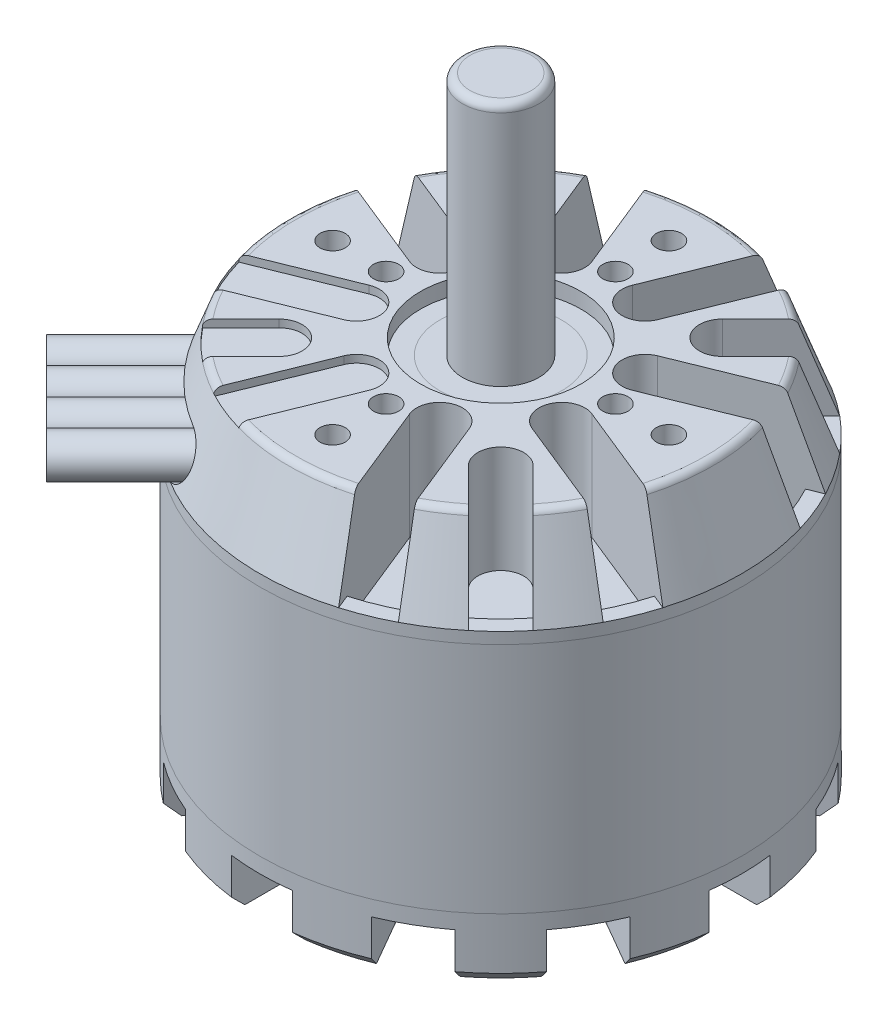
SolidWorks part; units mm, degrees
ref_plane "Front" through (0, 0, 0) normal (0, 0, 1) x (1, 0, 0)
ref_plane "Top" through (0, 0, 0) normal (0, 1, 0) x (1, 0, 0)
ref_plane "Right" through (0, 0, 0) normal (1, 0, 0) x (0, 0, -1)
sketch "Sketch1" plane through (0, 0, 0) normal (0, 1, 0) x (1, 0, 0)
  circle A0 centre (0, 0) radius 31.5
  dimension "D1" = 63
extrude "Boss-Extrude1" add sketch "Sketch1" along normal blind 51.5
sketch "Sketch2" plane through (0, 0, 0) normal (0, -1, 0) x (1, 0, 0)
  circle A0 centre (0, 0) radius 14
  dimension "D1" = 28
extrude "Boss-Extrude2" add sketch "Sketch2" along normal blind 1.5
sketch "Sketch3" plane through (0, -1.5, 0) normal (0, -1, 0) x (1, 0, 0)
  point P0 (0, 11)
  point P5 (11, 0)
  point P6 (0, -11)
  point P7 (-11, 0)
  point P8 (0, 0)
  dimension "D1" = 11
  dimension "D2" = 4
hole_wizard "M4 Tapped Hole1" positions "Sketch5" profile "Sketch4" tap size "M4" standard "ISO"
sketch "Sketch5" plane through (0, -1.5, 0) normal (0, -1, 0) x (-1, 0, 0)
  point P0 (0, -11)
  point P3 (-11, 0)
  point P6 (0, 11)
  point P9 (11, 0)
sketch "Sketch4" plane through (0, -1.5, 11) normal (1, 0, 0) x (0, 0, -1)
  line L0 (0, 0) -> (0, 12.4914)
  line L1 (0, 12.4914) -> (1.65, 11.5)
  line L2 (1.65, 11.5) -> (1.65, 0)
  line L5 (1.65, 0) -> (0, 0)
  line L10 (0, 12.4914) -> (-1.65, 11.5) construction
  line L11 (0, -6.35) -> (0, 107.95) construction
  dimension "Tap Drill Dia." = 3.3
  dimension "Tap Drill Depth" = 11.5
  dimension "Drill Angle" = 118
cosmetic thread "Hole Thread1" parameters "D1"=8, "D2"=4
cosmetic thread "Hole Thread2" parameters "D1"=8, "D2"=4
cosmetic thread "Hole Thread3" parameters "D1"=8, "D2"=4
cosmetic thread "Hole Thread4" parameters "D1"=8, "D2"=4
sketch "Sketch6" plane through (0, 0, 0) normal (0, -1, 0) x (1, 0, 0)
  line L0 (0, 31.5) -> (0, 18) construction
  line L1 (-4, 18) -> (-4, 31.245)
  line L2 (4, 18) -> (4, 31.245)
  line L3 (18, 4) -> (31.245, 4)
  line L4 (18, -4) -> (31.245, -4)
  line L5 (31.5, 0) -> (18, 0) construction
  line L6 (4, -18) -> (4, -31.245)
  line L7 (-4, -18) -> (-4, -31.245)
  line L8 (0, -31.5) -> (0, -18) construction
  line L9 (-18, -4) -> (-31.245, -4)
  line L10 (-18, 4) -> (-31.245, 4)
  line L11 (-31.5, 0) -> (-18, 0) construction
  line L12 (0, 0) -> (-15.75, 27.2798) construction
  line L13 (-19.0866, 25.059) -> (-14.9641, 17.9186)
  line L14 (-12.1584, 29.059) -> (-8.0359, 21.9186)
  line L15 (25.059, 19.0866) -> (17.9186, 14.9641)
  line L16 (29.059, 12.1584) -> (21.9186, 8.0359)
  line L17 (0, 0) -> (27.2798, 15.75) construction
  line L18 (19.0866, -25.059) -> (14.9641, -17.9186)
  line L19 (12.1584, -29.059) -> (8.0359, -21.9186)
  line L20 (0, 0) -> (15.75, -27.2798) construction
  line L21 (-25.059, -19.0866) -> (-17.9186, -14.9641)
  line L22 (-29.059, -12.1584) -> (-21.9186, -8.0359)
  line L23 (0, 0) -> (-27.2798, -15.75) construction
  line L24 (-22.2739, 22.2739) -> (22.2739, -22.2739) construction
  line L25 (-25.059, 19.0866) -> (-17.9186, 14.9641)
  line L26 (-29.059, 12.1584) -> (-21.9186, 8.0359)
  line L27 (19.0866, 25.059) -> (14.9641, 17.9186)
  line L28 (12.1584, 29.059) -> (8.0359, 21.9186)
  line L29 (25.059, -19.0866) -> (17.9186, -14.9641)
  line L30 (29.059, -12.1584) -> (21.9186, -8.0359)
  line L31 (-19.0866, -25.059) -> (-14.9641, -17.9186)
  line L32 (-12.1584, -29.059) -> (-8.0359, -21.9186)
  circle A0 centre (0, 0) radius 31.5 construction
  circle A1 centre (0, 18) radius 4
  circle A2 centre (0, 0) radius 14 construction
  circle A3 centre (0, 0) radius 31.5
  circle A4 centre (18, 0) radius 4
  circle A5 centre (0, -18) radius 4
  circle A6 centre (-18, 0) radius 4
  circle A7 centre (-11.5, 19.9186) radius 4
  circle A8 centre (19.9186, 11.5) radius 4
  circle A9 centre (11.5, -19.9186) radius 4
  circle A10 centre (-19.9186, -11.5) radius 4
  circle A11 centre (-19.9186, 11.5) radius 4
  circle A12 centre (11.5, 19.9186) radius 4
  circle A13 centre (19.9186, -11.5) radius 4
  circle A14 centre (-11.5, -19.9186) radius 4
  point P38 (0, 0)
  point P67 (0, 0)
  point P93 (0, 0)
  circle M11 centre (0, 0) radius 31.5
  dimension "D1" = 8
  dimension "D4" = 8
  dimension "D3" = 30
  dimension "D5" = 8.5
  dimension "D7" = 15
  dimension "D2" = 4
  dimension "D6" = 4
  dimension "D8" = 4
extrude "Cut-Extrude1" cut sketch "Sketch6" against normal blind 10 contours A7 L14 L13 M11 | A7 | A1 L2 L1 M11 | A1 | L28 A12 L27 M11 | A12 | A8 L16 L15 M11 | A8 | A4 L4 L3 M11 | A4 | A13 | L30 A13 L29 M11 | A9 | A9 L19 L18 M11 | A5 | A5 L7 L6 M11 | A14 | L32 A14 L31 M11 | A10 | A10 L22 L21 M11 | A6 | A6 L10 L9 M11 | A11 | L26 A11 L25 M11 region at (0, 0, 26.2399) region at (0, 0, 18) region at (-14.3517, 0, 24.8578) region at (14.3517, 0, 24.8578) region at (-11.5, 0, 19.9186) region at (11.5, 0, 19.9186) region at (-24.8578, 0, 14.3517) region at (24.8578, 0, 14.3517) region at (-19.9186, 0, 11.5) region at (19.9186, 0, 11.5) region at (-26.2399, 0, 0) region at (26.2399, 0, 0) region at (-18, 0, 0) region at (18, 0, 0) region at (-24.8578, 0, -14.3517) region at (-19.9186, 0, -11.5) region at (24.8578, 0, -14.3517) region at (-14.3517, 0, -24.8578) region at (19.9186, 0, -11.5) region at (-11.5, 0, -19.9186) region at (14.3517, 0, -24.8578) region at (0, 0, -26.2399) region at (11.5, 0, -19.9186) region at (0, 0, -18)
sketch "Sketch7" plane through (0, 10, 0) normal (0, -1, 0) x (1, 0, 0)
  circle A0 centre (0, 0) radius 31.5
  circle A1 centre (0, 0) radius 27
  dimension "5" = 54
extrude "Boss-Extrude3" add sketch "Sketch7" along normal blind 3.5
sketch "Sketch8" plane through (0, 0, 0) normal (0, 0, 1) x (1, 0, 0)
  line L0 (0, 51.5) -> (0, 0) construction
  line L1 (31.5, 51.5) -> (-31.5, 51.5) construction
  line L2 (29.059, 0) -> (21.9186, 0) construction
  line L3 (29.75, 0) -> (31.5, 0)
  line L4 (31.5, 0) -> (31.5, 1.75)
  line L5 (31.5, 6.5) -> (31.5, 51.5) construction
  line L6 (29.75, 0) -> (31.5, 1.75)
  point P5 (29.75, 0)
  dimension "D1" = 29.75
  dimension "D2" = 45
revolve "Cut-Revolve1" cut sketch "Sketch8" angle 360 about L0
sketch "Sketch9" plane through (0, 0, 0) normal (0, 0, 1) x (1, 0, 0)
  line L0 (0, 51.5) -> (0, 0) construction
  line L1 (31.5, 51.5) -> (-31.5, 51.5) construction
  line L2 (27.5, 51.5) -> (31.5, 40.5)
  line L3 (31.5, 6.5) -> (31.5, 51.5) construction
  line L4 (31.5, 40.5) -> (31.5, 51.5)
  line L5 (31.5, 51.5) -> (27.5, 51.5)
  point P5 (27.5, 51.5)
  dimension "D1" = 27.5
  dimension "D2" = 11
revolve "Cut-Revolve2" cut sketch "Sketch9" angle 360 about L0
fillet "Fillet1" radius 1 1 edges at (-27.5, 51.5, 0)
sketch "Sketch10" plane through (0, 51.5, 0) normal (0, 1, 0) x (1, 0, 0)
  circle A0 centre (0, 0) radius 10.5
  dimension "D1" = 21
extrude "Cut-Extrude2" cut sketch "Sketch10" against normal blind 2
sketch "Sketch11" plane through (0, 49.5, 0) normal (0, 1, 0) x (1, 0, 0)
  circle A0 centre (0, 0) radius 5
  dimension "D1" = 10
extrude "Boss-Extrude5" add sketch "Sketch11" along normal blind 32
fillet "Fillet2" radius 1 1 edges at (0, 81.5, 5)
sketch "Sketch12" plane through (0, 51.5, 0) normal (0, 1, 0) x (1, 0, 0)
  point P0 (0, 15)
  point P1 (0, 22)
  point P6 (15, 0)
  point P7 (22, 0)
  point P8 (0, -15)
  point P9 (0, -22)
  point P10 (-15, 0)
  point P11 (-22, 0)
  point P12 (0, 0)
  dimension "D1" = 15
  dimension "D2" = 22
  dimension "D3" = 4
hole_wizard "M4 Tapped Hole2" positions "Sketch14" profile "Sketch13" tap size "M4" standard "ISO"
sketch "Sketch14" plane through (0, 51.5, 0) normal (0, 1, 0) x (1, 0, 0)
  point P0 (0, 15)
  point P3 (0, 22)
  point P6 (15, 0)
  point P9 (22, 0)
  point P12 (0, -15)
  point P15 (0, -22)
  point P18 (-15, 0)
  point P21 (-22, 0)
sketch "Sketch13" plane through (0, 51.5, -15) normal (1, 0, 0) x (0, 0, 1)
  line L0 (0, 0) -> (0, 5.9914)
  line L1 (0, 5.9914) -> (1.65, 5)
  line L2 (1.65, 5) -> (1.65, 0)
  line L5 (1.65, 0) -> (0, 0)
  line L10 (0, 5.9914) -> (-1.65, 5) construction
  line L11 (0, -6.35) -> (0, 107.95) construction
  dimension "Tap Drill Dia." = 3.3
  dimension "Tap Drill Depth" = 5
  dimension "Drill Angle" = 118
cosmetic thread "Hole Thread5" parameters "D1"=5, "D2"=4
cosmetic thread "Hole Thread6" parameters "D1"=5, "D2"=4
cosmetic thread "Hole Thread7" parameters "D1"=5, "D2"=4
cosmetic thread "Hole Thread8" parameters "D1"=5, "D2"=4
cosmetic thread "Hole Thread9" parameters "D1"=5, "D2"=4
cosmetic thread "Hole Thread10" parameters "D1"=5, "D2"=4
cosmetic thread "Hole Thread11" parameters "D1"=5, "D2"=4
cosmetic thread "Hole Thread12" parameters "D1"=5, "D2"=4
sketch "Sketch15" plane through (0, 51.5, 0) normal (0, 1, 0) x (1, 0, 0)
  line L0 (0, 0) -> (0, 26.7996) construction
  line L1 (0, 0) -> (22.2739, 22.2739) construction
  line L2 (12.3744, 16.617) -> (20.0513, 24.2939)
  line L3 (16.617, 12.3744) -> (24.2939, 20.0513)
  line L4 (16.617, -12.3744) -> (24.2939, -20.0513)
  line L5 (12.3744, -16.617) -> (20.0513, -24.2939)
  line L6 (-12.3744, -16.617) -> (-20.0513, -24.2939)
  line L7 (-16.617, -12.3744) -> (-24.2939, -20.0513)
  line L8 (-16.617, 12.3744) -> (-24.2939, 20.0513)
  line L9 (-12.3744, 16.617) -> (-20.0513, 24.2939)
  line L10 (0, 0) -> (-11.8156, 29.2) construction
  line L11 (-8.2199, 12.316) -> (-14.5428, 27.942)
  line L12 (-2.658, 14.5666) -> (-8.9809, 30.1926)
  line L13 (12.316, 8.2199) -> (27.942, 14.5428)
  line L14 (14.5666, 2.658) -> (30.1926, 8.9809)
  line L15 (8.2199, -12.316) -> (14.5428, -27.942)
  line L16 (2.658, -14.5666) -> (8.9809, -30.1926)
  line L17 (-12.316, -8.2199) -> (-27.942, -14.5428)
  line L18 (-14.5666, -2.658) -> (-30.1926, -8.9809)
  line L19 (-2.658, 14.5666) -> (-8.9809, 30.1926)
  line L20 (-8.2199, 12.316) -> (-14.5428, 27.942)
  line L21 (2.658, 14.5666) -> (8.9809, 30.1926)
  line L22 (8.2199, 12.316) -> (14.5428, 27.942)
  line L23 (14.5666, -2.658) -> (30.1926, -8.9809)
  line L24 (12.316, -8.2199) -> (27.942, -14.5428)
  line L25 (-2.658, -14.5666) -> (-8.9809, -30.1926)
  line L26 (-8.2199, -12.316) -> (-14.5428, -27.942)
  line L27 (-14.5666, 2.658) -> (-30.1926, 8.9809)
  line L28 (-12.316, 8.2199) -> (-27.942, 14.5428)
  circle A0 centre (0, 0) radius 26.7996 construction
  circle A1 centre (0, 0) radius 31.5 construction
  circle A2 centre (14.4957, 14.4957) radius 3
  circle A3 centre (14.4957, -14.4957) radius 3
  circle A4 centre (-14.4957, -14.4957) radius 3
  circle A5 centre (-14.4957, 14.4957) radius 3
  circle A6 centre (-5.4389, 13.4413) radius 3
  circle A7 centre (13.4413, 5.4389) radius 3
  circle A8 centre (5.4389, -13.4413) radius 3
  circle A9 centre (-13.4413, -5.4389) radius 3
  circle A10 centre (5.4389, 13.4413) radius 3
  circle A11 centre (13.4413, -5.4389) radius 3
  circle A12 centre (-5.4389, -13.4413) radius 3
  circle A13 centre (-13.4413, 5.4389) radius 3
  circle A14 centre (0, 0) radius 31.5
  circle A15 centre (0, 0) radius 27.7394
  point P36 (0, 0)
  point P62 (0, 0)
  point P87 (0, 0)
  circle M27 centre (0, 0) radius 26.7996
  dimension "D2" = 6
  dimension "D5" = 6
  dimension "D1" = 45
  dimension "D3" = 11
  dimension "D6" = 17
  dimension "D7" = 4
  dimension "`" = 5
  dimension "D4" = 4
  dimension "D8" = 4
extrude "Cut-Extrude3" cut sketch "Sketch15" against normal blind 14 contours L12 A14 L11 M27 | A6 L12 L11 M27 | A6 | A10 | L21 A10 L22 M27 | L22 A14 L21 M27 | L3 A14 L2 M27 | A2 L3 L2 M27 | A2 | A7 L14 L13 M27 | L14 A14 L13 M27 | A7 | A11 | L23 A11 L24 M27 | L24 A14 L23 M27 | L5 A14 L4 M27 | A3 L5 L4 M27 | A3 | A8 | A8 L16 L15 M27 | L16 A14 L15 M27 | A5 | A5 L9 L8 M27 | L9 A14 L8 M27 | L28 A14 L27 M27 | L27 A13 L28 M27 | A13 | L28 A15 L27 M27 | L9 A15 L8 M27 | L12 A15 L11 M27 | L22 A15 L21 M27 | L16 A15 L15 M27 | L5 A15 L4 M27 | L24 A15 L23 M27 | L14 A15 L13 M27 | L3 A15 L2 M27 region at (17.4956, 51.5, -17.4956) region at (14.4957, 51.5, -14.4957) region at (19.2434, 51.5, -19.2434) region at (20.9082, 51.5, -20.9082) region at (10.208, 51.5, -25.2272) region at (8.1686, 51.5, -20.1872) region at (11.0911, 51.5, -27.4097) region at (20.1872, 51.5, -8.1686) region at (25.2272, 51.5, -10.208) region at (5.4389, 51.5, -13.4413) region at (27.4097, 51.5, -11.0911) region at (13.4413, 51.5, -5.4389) region at (-10.208, 51.5, -25.2272) region at (-8.1686, 51.5, -20.1872) region at (-11.0911, 51.5, -27.4097) region at (-5.4389, 51.5, -13.4413) region at (20.1872, 51.5, 8.1686) region at (25.2272, 51.5, 10.208) region at (-19.2434, 51.5, -19.2434) region at (-17.4956, 51.5, -17.4956) region at (27.4097, 51.5, 11.0911) region at (-20.9082, 51.5, -20.9082) region at (13.4413, 51.5, 5.4389) region at (-14.4957, 51.5, -14.4957) region at (17.4956, 51.5, 17.4956) region at (19.2434, 51.5, 19.2434) region at (-25.2272, 51.5, -10.208) region at (-20.1872, 51.5, -8.1686) region at (20.9082, 51.5, 20.9082) region at (-27.4097, 51.5, -11.0911) region at (14.4957, 51.5, 14.4957) region at (-13.4413, 51.5, -5.4389) region at (8.1686, 51.5, 20.1872) region at (10.208, 51.5, 25.2272) region at (11.0911, 51.5, 27.4097) region at (5.4389, 51.5, 13.4413)
sketch "Sketch16" plane through (0, 37.5, 0) normal (0, 1, 0) x (1, 0, 0)
  circle A0 centre (0, 0) radius 29.5
  circle A1 centre (0, 0) radius 31.5
  dimension "D1" = 59
extrude "Boss-Extrude6" add sketch "Sketch16" along normal blind 3
extrude "Cut-Extrude4" cut sketch "Sketch15<3>" against normal blind 1 contours A9 | A9 L18 L17 M27 | L18 A15 L17 M27 | L7 A15 L6 M27 | A4 L7 L6 M27 | A4 | A12 | L25 A12 L26 M27 | L26 A15 L25 M27 region at (-25.2272, 51.5, 10.208) region at (-20.1872, 51.5, 8.1686) region at (-13.4413, 51.5, 5.4389) region at (-8.1686, 51.5, 20.1872) region at (-10.208, 51.5, 25.2272) region at (-19.2434, 51.5, 19.2434) region at (-17.4956, 51.5, 17.4956) region at (-5.4389, 51.5, 13.4413) region at (-14.4957, 51.5, 14.4957)
sketch "Sketch15<3>" plane through (0, 51.5, 0) normal (0, 1, 0) x (1, 0, 0) same geometry as "Sketch15"
sketch "Sketch18" plane through (2.1213, 0, -2.1213) normal (-0.7071, 0, 0.7071) x (0.7071, 0, 0.7071)
  line L0 (-7, 43.5) -> (7, 43.5) construction
  line L2 (0, 81.5) -> (0, 34.4676) construction
  line L3 (4, 81.5) -> (-4, 81.5) construction
  line L4 (-7, 46.5) -> (7, 46.5)
  line L5 (-7, 40.5) -> (7, 40.5)
  line L6 (-27.6999, 40.5) -> (27.6999, 40.5) construction
  circle A0 centre (7, 43.5) radius 3
  circle A1 centre (-7, 43.5) radius 3
  dimension "D2" = 6
  dimension "D3" = 6
  dimension "D4" = 14
  dimension "D5" = 7
extrude "Cut-Extrude5" cut sketch "Sketch18" along normal blind 40 contours A1 | A1 L5 A0 L4 | A0 region at (2.1213, 43.5, -2.1213) region at (-2.8284, 43.5, -7.0711) region at (7.0711, 43.5, 2.8284)
sketch "Sketch19" plane through (2.1213, 0, -2.1213) normal (-0.7071, 0, 0.7071) x (0.7071, 0, 0.7071)
  circle A0 centre (-7.5, 43.5) radius 2.5
  circle A1 centre (-2.5, 43.5) radius 2.5
  circle A2 centre (2.5, 43.5) radius 2.5
  circle A3 centre (7.5, 43.5) radius 2.5
  arc A4 (7, 40.5) -> (7, 46.5) centre (7, 43.5) ccw construction
  arc A5 (-7, 46.5) -> (-7, 40.5) centre (-7, 43.5) ccw construction
  dimension "D1" = 5
  dimension "D2" = 5
  dimension "D3" = 5
  dimension "D4" = 5
extrude "Boss-Extrude7" add sketch "Sketch19" along normal blind 45 separate body contours A0 | A1 | A2 | A3 region at (-3.182, 43.5, -7.4246) region at (7.4246, 43.5, 3.182) region at (3.8891, 43.5, -0.3536) region at (0.3536, 43.5, -3.8891)
sketch "Sketch20" plane through (0, 0, 0) normal (1, 0, 0) x (0, 0, -1)
  line L0 (-45.7336, 8.5) -> (64.8377, 8.5)
  line L1 (-14, 0) -> (0, 0) construction
  line L2 (-51.0726, 39) -> (61.6662, 39)
  line L3 (8.2199, 51.5) -> (12.7702, 51.5) construction
  dimension "D1" = 8.5
  dimension "D2" = 12.5
split line "Split Line1"
sketch "Sketch21" plane through (0, 49.5, 0) normal (0, 1, 0) x (1, 0, 0)
  circle A0 centre (0, 0) radius 8
  dimension "D1" = 16
split line "Split Line2"
